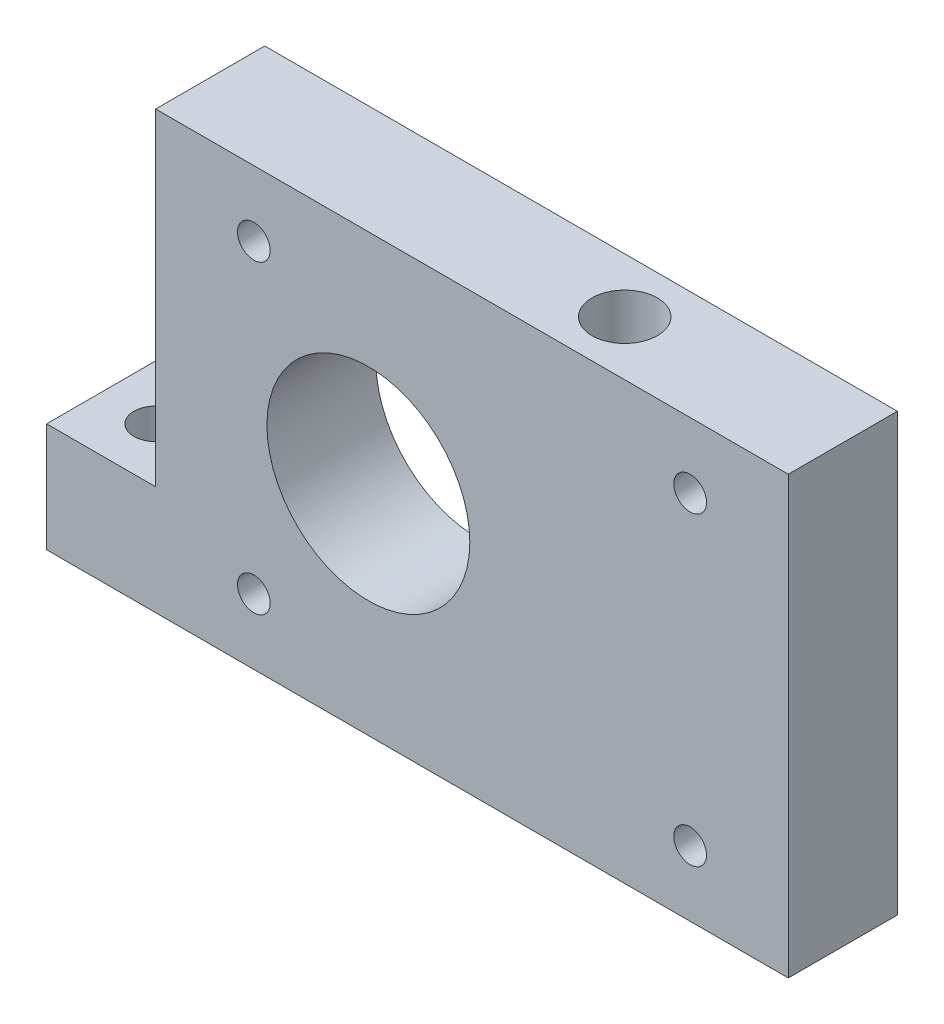
SolidWorks part; units mm, degrees
material "ABS"
ref_plane "Front Plane" through (0, 0, 0) normal (0, 0, 1) x (1, 0, 0)
ref_plane "Top Plane" through (0, 0, 0) normal (0, 1, 0) x (1, 0, 0)
ref_plane "Right Plane" through (0, 0, 0) normal (1, 0, 0) x (0, 0, -1)
sketch "Sketch1" plane through (0, 0, 0) normal (0, 0, 1) x (1, 0, 0)
  circle A0 centre (-49, 7.836) radius 1.5
  circle A1 centre (-49, 7.836) radius 3.9
  circle A2 centre (-49, 35.836) radius 1.5
  circle A3 centre (-49, 35.836) radius 3.9
  circle A4 centre (-9, 35.836) radius 1.5
  circle A5 centre (-9, 35.836) radius 3.9
  circle A6 centre (-9, 7.836) radius 1.5
  circle A7 centre (-9, 7.836) radius 3.9
extrude "Boss-Extrude1" add sketch "Sketch1" along normal up to surface (10.0616 mm away)
sketch "Sketch2" plane through (0, 0, -1.8) normal (0, 0, 1) x (1, 0, 0)
  line L0 (-58, 1.836) -> (0, 1.836) construction
  line L1 (-58, 41.836) -> (0, 41.836)
  line L2 (-58, 41.836) -> (-58, 1.836)
  line L3 (-58, 1.836) -> (0, 1.836)
  line L4 (0, 41.836) -> (0, 1.836)
  line L5 (-58, 41.836) -> (0, 1.836) construction
  line L6 (-58, 1.836) -> (0, 41.836) construction
  point P4 (-29, 21.836)
  circle M1 centre (-9, 7.836) radius 3.9
  circle M2 centre (-9, 35.836) radius 3.9
  circle M3 centre (-49, 35.836) radius 3.9
  circle M4 centre (-49, 7.836) radius 3.9
  circle M5 centre (-38.5, 21.836) radius 9.3
  line M6 (0, 1.836) -> (0, 5.29)
  line M7 (0, 5.29) -> (0, 38.4413)
  line M8 (0, 38.4413) -> (0, 41.836)
  line M9 (0, 41.836) -> (-58, 41.836)
  line M10 (-58, 41.836) -> (-58, 1.836)
  line M11 (-58, 1.836) -> (0, 1.836)
extrude "Boss-Extrude2" add sketch "Sketch2" against normal blind 10 from surface contours M11 M6 M7 M8 M9 M10 M2 M4 M5 M3 M1 region at (-27.6101, 21.836, -1.8) starting at face at (-50.5, 35.836, 10.0616)
sketch "Sketch4" plane through (0, 41.836, 0) normal (0, 1, 0) x (1, 0, 0)
  line L0 (0, -5.0616) -> (-58, -5.0616) construction
  line L1 (0, -0.0616) -> (0, -10.0616) construction
  line L2 (-58, -0.0616) -> (-58, -10.0616) construction
  circle A0 centre (-20, -5.0616) radius 3
  circle A1 centre (-20, -5.0616) radius 2
  dimension "D1" = 6
  dimension "D2" = 4
  dimension "D3" = 20
extrude "Cut-Extrude1" cut sketch "Sketch4" against normal blind 25 contours L0 A0 A1 | A1 L0 | A0 L0 A1 | L0 A1 region at (-20, 41.836, 7.9945) region at (-17.5, 41.836, 4.9945) region at (-20, 41.836, 5.9104) region at (-20, 41.836, 4.2127)
extrude "Cut-Extrude2" cut sketch "Sketch4<3>" against normal through all contours L0 A1 | A1 L0 region at (-20, 41.836, 5.9104) region at (-20, 41.836, 4.2127)
sketch "Sketch4<3>" plane through (0, 41.836, 0) normal (0, 1, 0) x (1, 0, 0) same geometry as "Sketch4"
sketch "Sketch5" plane through (0, 1.836, 0) normal (0, 1, 0) x (1, 0, 0)
  line L0 (0, -10.0616) -> (-58, -10.0616) construction
  line L1 (-58, -0.0616) -> (-68, -0.0616)
  line L2 (-58, -0.0616) -> (-58, -10.0616)
  line L3 (-58, -10.0616) -> (-68, -10.0616)
  line L4 (-68, -0.0616) -> (-68, -10.0616)
  line L5 (-58, -0.0616) -> (-68, -10.0616) construction
  line L6 (-58, -10.0616) -> (-68, -0.0616) construction
  circle A0 centre (-63, -5.0616) radius 2
  point P4 (-63, -5.0616)
  dimension "D2" = 4
  dimension "D1" = 10
  dimension "D3" = 0
extrude "Boss-Extrude3" add sketch "Sketch5" along normal blind 10
